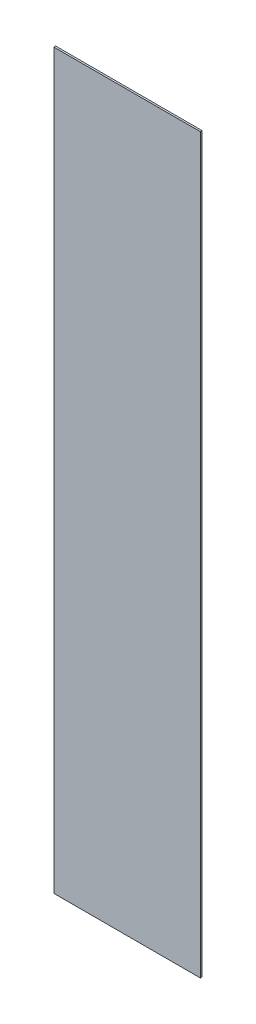
SolidWorks part; units mm, degrees
ref_plane "Front Plane" through (0, 0, 0) normal (0, 0, 1) x (1, 0, 0)
ref_plane "Top Plane" through (0, 0, 0) normal (0, 1, 0) x (1, 0, 0)
ref_plane "Right Plane" through (0, 0, 0) normal (1, 0, 0) x (0, 0, -1)
sketch "Sketch1" plane through (0, 0, 0) normal (0, 0, 1) x (1, 0, 0)
  line L1 (0, 0) -> (50.8, 0)
  line L2 (0, 0) -> (0, 254)
  line L3 (0, 254) -> (50.8, 254)
  line L4 (50.8, 0) -> (50.8, 254)
  dimension "D1" = 50.8
  dimension "D2" = 254
extrude "Boss-Extrude1" add sketch "Sketch1" along normal blind 0.635
